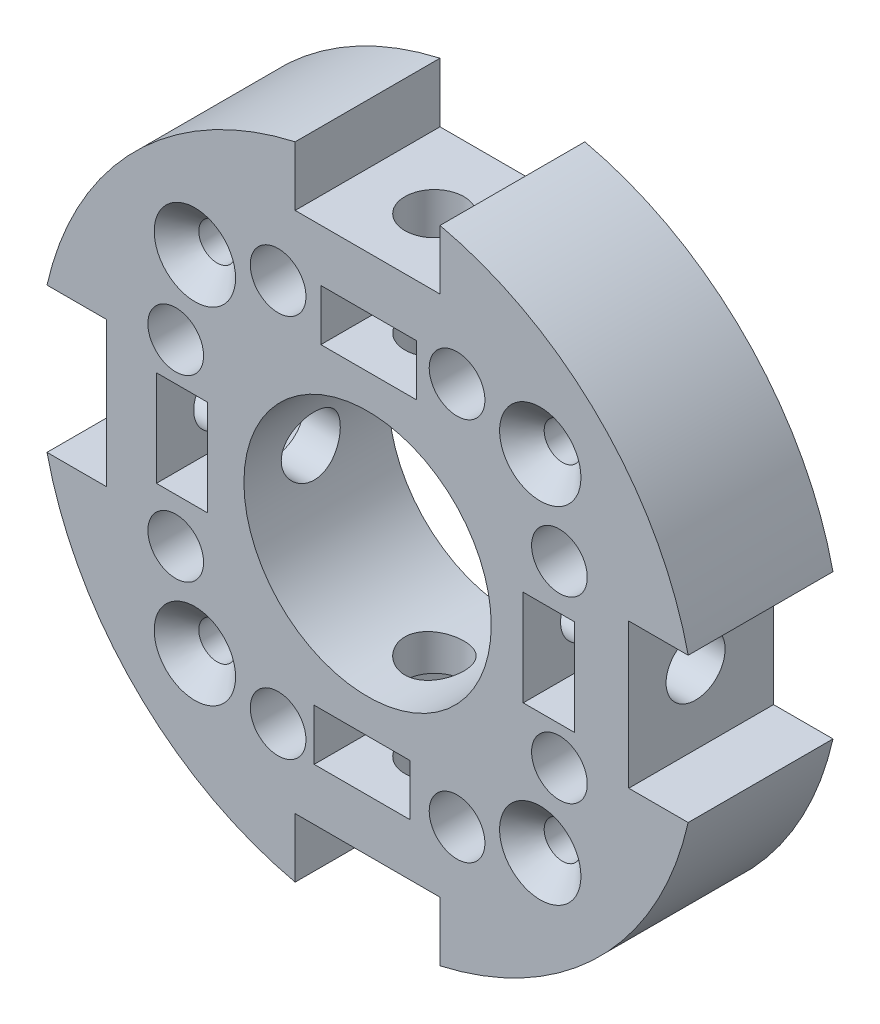
SolidWorks part; units mm, degrees
ref_plane "Plan de face" through (0, 0, 0) normal (0, 0, 1) x (1, 0, 0)
ref_plane "Plan de dessus" through (0, 0, 0) normal (0, 1, 0) x (1, 0, 0)
ref_plane "Plan de droite" through (0, 0, 0) normal (1, 0, 0) x (0, 0, -1)
sketch "Esquisse1" plane through (0, 0, 0) normal (0, 0, 1) x (1, 0, 0)
  line L36 (-18.9562, 4.6) -> (-14.3562, 4.6)
  line L52 (-0.2997, 0.2997) -> (-35355.6388, 35355.6388) construction
  line L54 (0, -1000) -> (0, 49000) construction
  line L60 (6, 23.9414) -> (6, 29.3939) construction
  line L61 (-14.3562, -4) -> (-14.3562, 4.6)
  line L62 (-18.6562, -3.7) -> (-14.6562, -3.7) construction
  line L63 (-18.6562, -3.7) -> (-18.6562, 4.3) construction
  line L64 (-18.6562, 4.3) -> (-14.6562, 4.3) construction
  line L65 (-14.6562, -3.7) -> (-14.6562, 4.3) construction
  line L66 (-18.6562, -3.7) -> (-14.6562, 4.3) construction
  line L67 (-23.9414, -6) -> (-29.3939, -6) construction
  line L68 (-23.9414, -6) -> (-23.9414, 6) construction
  line L69 (-23.9414, 6) -> (-29.3939, 6) construction
  line L71 (-6, 23.9414) -> (6, 23.9414) construction
  line L72 (-6, 23.9414) -> (-6, 29.3939)
  line L73 (-4.2406, 9.094) -> (-21135.1537, 45324.4833) construction
  line L74 (-23.4414, -6.5) -> (-23.4414, 6.5)
  line L75 (-23.4414, 6.5) -> (-28.775, 6.5)
  line L76 (-6.5, 23.4414) -> (-6.5, 28.775)
  line L77 (-18.6562, 4.3) -> (-14.6562, -3.7) construction
  line L78 (-18.9562, -4) -> (-14.3562, -4)
  line L79 (-18.9562, -4) -> (-18.9562, 4.6)
  line L80 (4.4068, 18.7629) -> (4.4068, 14.1629)
  line L81 (-4.1932, 14.1629) -> (4.4068, 14.1629)
  line L82 (-4.1932, 18.7629) -> (-4.1932, 14.1629)
  line L83 (-4.1932, 18.7629) -> (4.4068, 18.7629)
  line L84 (18.5697, -4.6) -> (13.9697, -4.6)
  line L85 (13.9697, 4) -> (13.9697, -4.6)
  line L86 (18.5697, 4) -> (13.9697, 4)
  line L87 (18.5697, 4) -> (18.5697, -4.6)
  line L88 (-4.7932, -18.7629) -> (-4.7932, -14.1629)
  line L89 (3.8068, -14.1629) -> (-4.7932, -14.1629)
  line L90 (3.8068, -18.7629) -> (3.8068, -14.1629)
  line L91 (3.8068, -18.7629) -> (-4.7932, -18.7629)
  line L92 (23.9414, -6) -> (29.3939, -6) construction
  line L93 (23.9414, 6) -> (23.9414, -6) construction
  line L94 (23.9414, 6) -> (29.3939, 6) construction
  line L95 (-6, -23.9414) -> (-6, -29.3939) construction
  line L96 (6, -23.9414) -> (-6, -23.9414) construction
  line L97 (6, -23.9414) -> (6, -29.3939) construction
  line L98 (-6.5, 23.4414) -> (6.5, 23.4414)
  line L99 (6.5, 23.4414) -> (6.5, 28.775)
  line L100 (23.4414, 6.5) -> (28.775, 6.5)
  line L101 (23.4414, 6.5) -> (23.4414, -6.5)
  line L102 (23.4414, -6.5) -> (28.775, -6.5)
  line L103 (6.5, -23.4414) -> (6.5, -28.775)
  line L104 (6.5, -23.4414) -> (-6.5, -23.4414)
  line L105 (-6.5, -23.4414) -> (-6.5, -28.775)
  line L106 (-23.4414, -6.5) -> (-28.775, -6.5)
  circle A1 centre (0, 0) radius 11.1
  circle A2 centre (-15.5, 15.5) radius 1.65
  circle A3 centre (15.5, 15.5) radius 1.65
  circle A4 centre (15.5, -15.5) radius 1.65
  circle A5 centre (-15.5, -15.5) radius 1.65
  arc A18 (-29.3939, -6) -> (-6, -29.3939) centre (0, 0) ccw construction
  circle A21 centre (-8.0297, 17.2198) radius 2.5
  arc A23 (-6, 29.3939) -> (-29.3939, 6) centre (0, 0) ccw construction
  arc A24 (29.3939, 6) -> (6, 29.3939) centre (0, 0) ccw construction
  arc A25 (6, -29.3939) -> (29.3939, -6) centre (0, 0) ccw construction
  circle A26 centre (8.0297, 17.2198) radius 2.5
  circle A27 centre (17.2198, 8.0297) radius 2.5
  circle A28 centre (17.2198, -8.0297) radius 2.5
  circle A29 centre (8.0297, -17.2198) radius 2.5
  circle A30 centre (-8.0297, -17.2198) radius 2.5
  circle A31 centre (-17.2198, -8.0297) radius 2.5
  circle A32 centre (-17.2198, 8.0297) radius 2.5
  arc A33 (-6.5, 28.775) -> (-28.775, 6.5) centre (0, 0) ccw
  arc A34 (28.775, 6.5) -> (6.5, 28.775) centre (0, 0) ccw
  arc A35 (6.5, -28.775) -> (28.775, -6.5) centre (0, 0) ccw
  arc A36 (-28.775, -6.5) -> (-6.5, -28.775) centre (0, 0) ccw
  point P1 (-27.9414, 0)
  point P22 (0, 0)
  point P32 (0, 0)
  point P33 (0, 0)
  point P39 (-16.6562, 0.3)
  point P73 (0, 0)
  point P75 (0, 0)
  point P90 (0, 0)
  dimension "D2" = 22.2
  dimension "D7" = 3.3
  dimension "D14" = 0.5
  dimension "D18" = 8
  dimension "D6" = 5.4525
  dimension "D15" = 5
  dimension "D4" = 60
  dimension "D11" = 4
  dimension "D3" = 12
  dimension "D5" = 21.9203
  dimension "D9" = 0.3
  dimension "D10" = 4
  dimension "D16" = 45
  dimension "D17" = 19
  dimension "D19" = 4
  dimension "D12" = 25
  dimension "D8" = 4
  dimension "D13" = 4
extrude "Boss.-Extru.1" add sketch "Esquisse1" along normal blind 13 contours A1 A2 A3 | A1 A5 A4 region at (-22.6275, 0, 0)
chamfer "Chanfrein1" distance 2 angle 45 4 edges at (-13.85, -15.5, 13) (17.15, -15.5, 13) (17.15, 15.5, 13) (-13.85, 15.5, 13)
sketch "Esquisse2" plane through (-14.3562, 0, 0) normal (-1, 0, 0) x (0, 0, 1)
  line L1 (13, -6.5) -> (13, 6.5) construction
  circle A0 centre (7, 0) radius 2.65
  dimension "D1" = 5.3
  dimension "D2" = 6
extrude "Enlèv. mat.-Extru.1" cut sketch "Esquisse2" against normal up to next and the other way through all
pattern_circular "Répétition circulaire1" count 4 over 360 about axis through (0, 0, 13) along (0, 0, 1) of "Enlèv. mat.-Extru.1"
